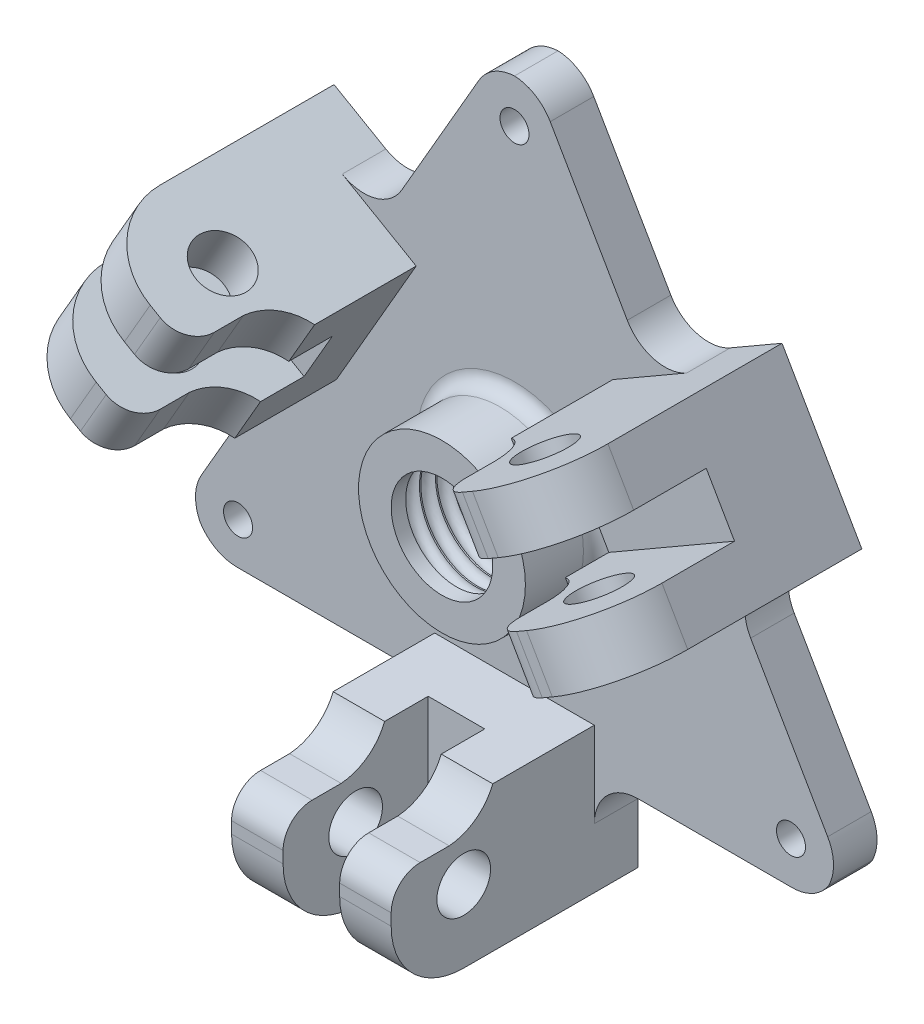
SolidWorks part; units mm, degrees
note: The reader was unsure of these and kept them because the rebuilt part matched: shared geometry of "Sketch1<7>".
ref_plane "Front Plane" through (0, 0, 0) normal (0, 0, 1) x (1, 0, 0)
ref_plane "Top Plane" through (0, 0, 0) normal (0, 1, 0) x (1, 0, 0)
ref_plane "Right Plane" through (0, 0, 0) normal (1, 0, 0) x (0, 0, -1)
sketch "Sketch1" plane through (0, 0, 0) normal (0, 0, 1) x (1, 0, 0)
  circle A2 centre (0, 0) radius 4
  circle A53 centre (0, 0) radius 5.75
  circle A56 centre (0, 0) radius 25
  circle A57 centre (0, 0) radius 22 construction
  circle A58 centre (0, 22) radius 1
  circle A59 centre (19.0526, -11) radius 1
  circle A60 centre (-19.0526, -11) radius 1
  point P15 (0, 0)
  point P28 (0, 0)
  point P44 (0, 0)
  point P72 (0, 0)
  dimension "D1" = 44
  dimension "D2" = 2
  dimension "D3" = 8
  dimension "D4" = 11.5
  dimension "D5" = 3
  dimension "D8" = 50
extrude "Boss-Extrude1" add sketch "Sketch1" along normal blind 3
extrude "Boss-Extrude2" add sketch "Sketch1<7>" along normal blind 8 contours A53 A2
sketch "Sketch1<7>" plane through (0, 0, 0) normal (0, 0, 1) x (1, 0, 0) same geometry as "Sketch1"
sketch "Sketch53" plane through (0, 0, 0) normal (0, 0, -1) x (-1, 0, 0)
  circle A0 centre (0, 0) radius 4 construction
  circle A1 centre (0, 0) radius 4
curve "Helix/Spiral1" pitch 1.1 height 8.8 turns 8
sweep "Cut-Sweep1" cut path "Helix/Spiral1" align with end faces yes circular profile diameter 1 parameters "D3"=1
sketch "Sketch59" plane through (0, 0, 8) normal (0, 0, 1) x (1, 0, 0)
  circle A0 centre (0, 0) radius 5
  circle A1 centre (0, 0) radius 3.5
  dimension "D1" = 10
  dimension "D2" = 7
extrude "Boss-Extrude4" add sketch "Sketch59" against normal blind 1
sketch "Sketch66" plane through (0, 0, 0) normal (0, 0, -1) x (-1, 0, 0)
  circle A0 centre (0, 0) radius 5
  dimension "D1" = 10
extrude "Cut-Extrude3" cut sketch "Sketch66" against normal blind 3 draft 45
sketch "Sketch67" plane through (0, 0, 3) normal (0, 0, 1) x (1, 0, 0)
  line L0 (0, 0) -> (0, 22) construction
  line L1 (0, 0) -> (19.0526, -11) construction
  line L2 (0, 0) -> (13.8564, 8) construction
  line L3 (15.4365, 15.2631) -> (20.9365, 5.7369)
  line L4 (15.4365, 15.2631) -> (6.7763, 10.2631)
  line L5 (20.9365, 5.7369) -> (12.2763, 0.7369)
  line L6 (6.7763, 10.2631) -> (12.2763, 0.7369)
  line L7 (15.4365, 15.2631) -> (12.2763, 0.7369) construction
  line L8 (20.9365, 5.7369) -> (6.7763, 10.2631) construction
  line L9 (5.5, -21) -> (-5.5, -21)
  line L10 (5.5, -21) -> (5.5, -11)
  line L11 (5.5, -11) -> (-5.5, -11)
  line L12 (-5.5, -21) -> (-5.5, -11)
  line L13 (-20.9365, 5.7369) -> (-15.4365, 15.2631)
  line L14 (-20.9365, 5.7369) -> (-12.2763, 0.7369)
  line L15 (-12.2763, 0.7369) -> (-6.7763, 10.2631)
  line L16 (-15.4365, 15.2631) -> (-6.7763, 10.2631)
  point P22 (0, 0)
  dimension "D1" = 60
  dimension "D2" = 10
  dimension "D3" = 11
  dimension "D5" = 16
  dimension "D4" = 3
extrude "Boss-Extrude5" add sketch "Sketch67" along normal blind 14
sketch "Sketch68" plane through (0, 0, 17) normal (0, 0, 1) x (1, 0, 0)
  line L7 (18.1865, 10.5) -> (9.5263, 5.5) construction
  line L13 (8.5513, 7.1887) -> (19.3235, 13.4081)
  line L14 (8.5513, 7.1887) -> (10.5013, 3.8113)
  line L15 (19.3235, 13.4081) -> (21.2735, 10.0306)
  line L16 (15.4365, 15.2631) -> (6.7763, 10.2631)
  line L17 (6.7763, 10.2631) -> (12.2763, 0.7369)
  line L18 (12.2763, 0.7369) -> (20.9365, 5.7369)
  line L19 (20.9365, 5.7369) -> (15.4365, 15.2631)
  line L20 (15.4365, 15.2631) -> (6.7763, 10.2631) construction
  line L21 (6.7763, 10.2631) -> (12.2763, 0.7369) construction
  line L22 (12.2763, 0.7369) -> (20.9365, 5.7369) construction
  line L23 (20.9365, 5.7369) -> (15.4365, 15.2631) construction
  line L24 (10.5013, 3.8113) -> (21.2735, 10.0306)
  line L25 (8.5513, 7.1887) -> (21.2735, 10.0306) construction
  line L26 (19.3235, 13.4081) -> (10.5013, 3.8113) construction
  line L27 (1.95, -11) -> (1.95, -23.4387)
  line L28 (1.95, -11) -> (-1.95, -11)
  line L29 (-1.95, -11) -> (-1.95, -23.4387)
  line L30 (1.95, -23.4387) -> (-1.95, -23.4387)
  line L31 (-10.5013, 3.8113) -> (-21.2735, 10.0306)
  line L32 (-10.5013, 3.8113) -> (-8.5513, 7.1887)
  line L33 (-8.5513, 7.1887) -> (-19.3235, 13.4081)
  line L34 (-21.2735, 10.0306) -> (-19.3235, 13.4081)
  point P6 (9.5263, 5.5)
  point P7 (14.9124, 8.6097)
  point P26 (0, 0)
  dimension "D1" = 0
  dimension "D2" = 3.9
  dimension "D3" = 3
extrude "Cut-Extrude4" cut sketch "Sketch68" against normal blind 10
sketch "Sketch70" plane through (2.75, -4.7631, 0) normal (0.5, -0.866, 0) x (0.866, 0.5, 0)
  line L0 (11, 17) -> (21, 17) construction
  line L1 (11, 17) -> (11, 3) construction
  line L2 (13.2, 13) -> (13.2, 17)
  line L3 (13.2, 17) -> (11, 17)
  line L4 (11, 17) -> (11, 10)
  circle A0 centre (16, 12) radius 1.85
  arc A2 (11, 10) -> (13.2, 13) centre (9.7092, 13.2533) ccw
  point P5 (16, 17)
  dimension "D1" = 3.7
  dimension "D3" = 2.2
  dimension "D4" = 7
  dimension "D6" = 3.5
  dimension "D2" = 5
  dimension "D5" = 4
extrude "Cut-Extrude5" cut sketch "Sketch70" against normal blind 15
pattern_circular "CirPattern1" count 3 over 360 about axis through (0, 0, 0) along (0, 0, 1) of "Cut-Extrude5"
fillet "Fillet1" radius 5 6 edges at (3.725, -21, 17) (-3.725, -21, 17) (20.049, 7.2741, 17) (16.324, 13.7259, 17) (-16.324, 13.7259, 17) (-20.049, 7.2741, 17)
fillet "Fillet2" radius 2 6 edges at (9.569, 9.8259, 17) (-9.569, 9.8259, 17) (-13.294, 3.3741, 17) (13.294, 3.3741, 17) (-3.725, -13.2, 17) (3.725, -13.2, 17)
sketch "Sketch71" plane through (0, 0, 3) normal (0, 0, 1) x (1, 0, 0)
  line L0 (-1.6261, 24.9471) -> (-9.272, 11.704)
  line L2 (0, 22) -> (0, 0) construction
  line L3 (1.6261, 24.9471) -> (9.272, 11.704)
  line L4 (22.4179, -11.0653) -> (14.772, 2.1778)
  line L5 (20.7917, -13.8818) -> (5.5, -13.8818)
  line L6 (-20.7917, -13.8818) -> (-5.5, -13.8818)
  line L7 (-22.4179, -11.0653) -> (-14.772, 2.1778)
  line L8 (-9.272, 11.704) -> (-15.4365, 15.2631)
  line L9 (-15.4365, 15.2631) -> (-20.9365, 5.7369)
  line L10 (-20.9365, 5.7369) -> (-14.772, 2.1778)
  line L11 (-5.5, -13.8818) -> (-5.5, -21)
  line L12 (-5.5, -11) -> (-5.5, -21) construction
  line L13 (-5.5, -21) -> (5.5, -21) construction
  line L14 (9.272, 11.704) -> (15.4365, 15.2631)
  line L15 (15.4365, 15.2631) -> (20.9365, 5.7369)
  line L16 (20.9365, 5.7369) -> (14.772, 2.1778)
  line L17 (-5.5, -21) -> (5.5, -21)
  line L18 (5.5, -21) -> (5.5, -13.8818)
  line L19 (-6.7763, 10.2631) -> (-15.4365, 15.2631) construction
  circle A0 centre (0, 22) radius 1 construction
  circle A1 centre (0, 0) radius 25
  circle A2 centre (0, 0) radius 25
  circle A3 centre (0, 22) radius 1
  point P23 (0, 0)
  dimension "D2" = 60
  dimension "D1" = 0
  dimension "D3" = 3
extrude "Cut-Extrude6" cut sketch "Sketch71" against normal blind 10
fillet "Fillet3" radius 3 12 edges at (-20.7917, -13.8818, 1.5) (-22.4179, -11.0653, 1.5) (20.7917, -13.8818, 1.5) (22.4179, -11.0653, 1.5) (1.6261, 24.9471, 1.5) (-1.6261, 24.9471, 1.5) (-14.772, 2.1778, 1.5) (-5.5, -13.8818, 1.5) (5.5, -13.8818, 1.5) (14.772, 2.1778, 1.5) (9.272, 11.704, 1.5) (-9.272, 11.704, 1.5)
fillet "Fillet4" radius 1 1 edges at (5.75, 0, 3)
